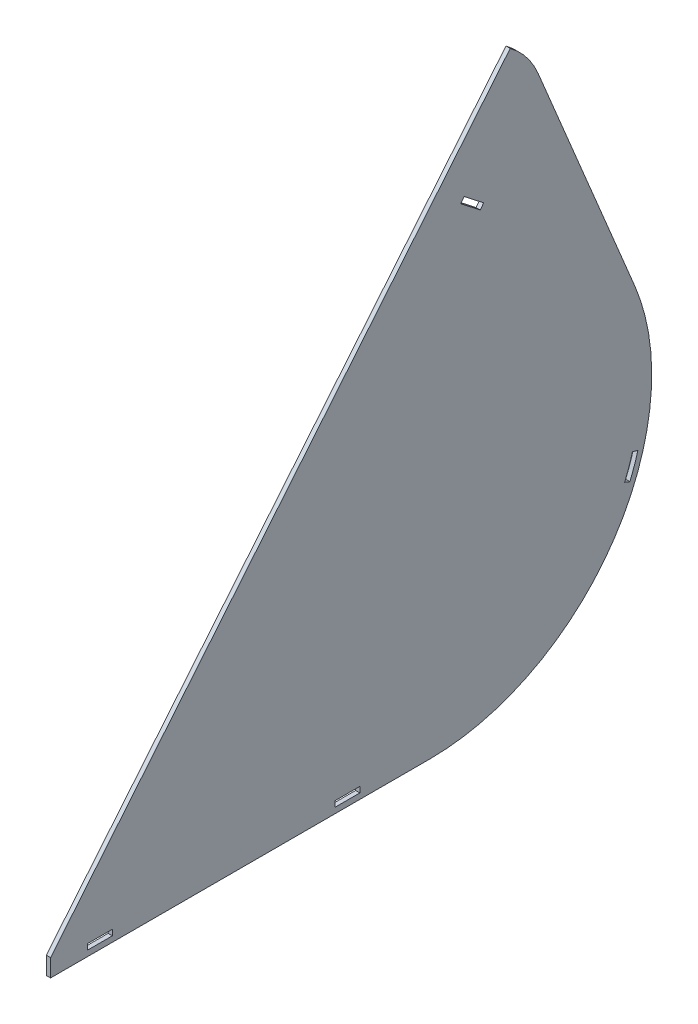
SolidWorks part; units mm, degrees
material "MS-Grade 350"
ref_plane "Front Plane" through (0, 0, 0) normal (0, 0, 1) x (1, 0, 0)
ref_plane "Top Plane" through (0, 0, 0) normal (0, 1, 0) x (1, 0, 0)
ref_plane "Right Plane" through (0, 0, 0) normal (1, 0, 0) x (0, 0, -1)
sketch "Sketch1" plane through (0, 0, 0) normal (1, 0, 0) x (0, 0, -1)
  line L0 (691.2634, 750.025) -> (828.1455, 420.9919)
  line L1 (537.3089, -15) -> (0, -15)
  line L2 (0, 10) -> (651.6871, 800.5139)
  line L18 (537.3089, -6) -> (537.3089, -15) construction
  line L19 (0, 10) -> (0, -15)
  arc A0 (537.3089, -15) -> (828.1455, 420.9919) centre (537.3089, 300) ccw
  arc A1 (691.2634, 750.025) -> (651.6871, 800.5139) centre (580.4685, 703.9328) ccw
  dimension "D10" = 120
  dimension "D3" = 315
  dimension "D2" = 64.1515
  dimension "D4" = 10
  dimension "D8" = 50.498
  dimension "D14" = 25
  dimension "D18" = 1024.5039
sheet metal parameters "Sheet-Metal1" thickness 6 parameters "D1"=92
base flange "Base-Flange1" sketch "Sketch1" thickness 6 reverse thickness direction no parameters "D1"=92
sketch "Sketch3" plane through (0, 0, 0) normal (1, 0, 0) x (0, 0, -1)
  line L3 (832.7179, 216.4387) -> (825.0351, 218.6692)
  line L4 (587.0441, 649.5568) -> (431.1206, 771.0809) construction
  line L5 (813.9996, 186.6716) -> (821.424, 183.6918)
  line L6 (52.6709, -7) -> (87.6709, -7)
  line L7 (87.6709, -7) -> (87.6709, 1)
  line L8 (87.6709, 1) -> (52.6709, 1)
  line L9 (52.6709, 1) -> (52.6709, -7)
  line L10 (403.5256, -7) -> (438.5256, -7)
  line L11 (438.5256, -7) -> (438.5256, 1)
  line L12 (438.5256, 1) -> (403.5256, 1)
  line L13 (403.5256, 1) -> (403.5256, -7)
  line L14 (581.5579, 644.9577) -> (609.1637, 623.4422)
  line L15 (609.1637, 623.4422) -> (614.0816, 629.7521)
  line L16 (614.0816, 629.7521) -> (586.4757, 651.2676)
  line L17 (586.4757, 651.2676) -> (581.5579, 644.9577)
  line L18 (584.0159, 644.0446) -> (587.7008, 648.7727) construction
  line L22 (0, -15) -> (537.3089, -15) construction
  line L27 (821.7306, 186.2626) -> (816.1741, 188.4927) construction
  line L28 (831.8782, 214.877) -> (826.1291, 216.5461) construction
  line L31 (406.0256, 0) -> (406.0256, -6) construction
  line L33 (55.1709, 0) -> (55.1709, -6) construction
  arc A2 (832.7179, 216.4387) -> (821.424, 183.6918) centre (537.3089, 300) cw
  arc A3 (825.0351, 218.6692) -> (813.9996, 186.6716) centre (537.3089, 300) cw
  arc A8 (537.3089, -15) -> (828.1455, 420.9919) centre (537.3089, 300) ccw construction
  dimension "D9" = 8
  dimension "D1" = 2.5
  dimension "D2" = 2.5
  dimension "D3" = 8
  dimension "D4" = 8
  dimension "D5" = 35
  dimension "D6" = 1
  dimension "D7" = 2.5
  dimension "D8" = 2.5
extrude "Cut-Extrude2" cut sketch "Sketch3" against normal blind 6
flat pattern "Flat-Pattern1" [suppressed]
sketch "Bend-Lines1" plane through (0, 0, 0) normal (0, 1, 0) x (1, 0, 0)
sketch3d "Bounding-Box1" [suppressed]
  line L0 (-172.2646, -1055.5466, 0) -> (491.832, -249.9087, 0) construction
  line L1 (-594.0414, -707.8711, 0) -> (70.0552, 97.7668, 0) construction
  line L2 (-172.2646, -1055.5466, 0) -> (-594.0414, -707.8711, 0) construction
  line L3 (491.832, -249.9087, 0) -> (70.0552, 97.7668, 0) construction
